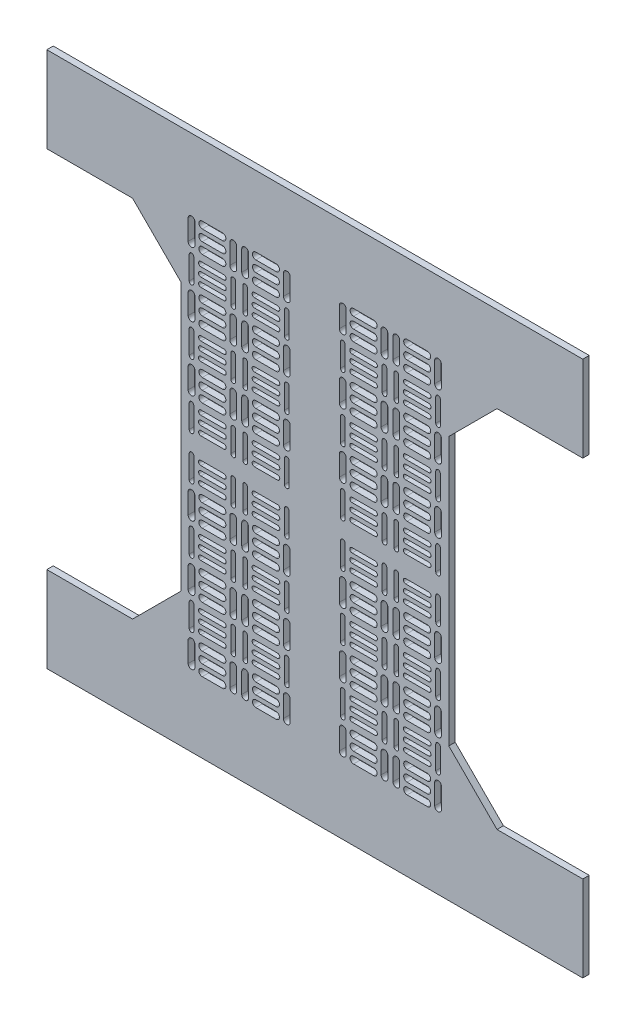
SolidWorks part; units mm, degrees
ref_plane "XY" through (0, 0, 0) normal (0, 0, 1) x (1, 0, 0)
ref_plane "-XZ" through (0, 0, 0) normal (0, 1, 0) x (1, 0, 0)
ref_plane "ZY" through (0, 0, 0) normal (1, 0, 0) x (0, 0, -1)
sketch "Esquisse1" plane through (0, 0, 0) normal (0, 0, 1) x (1, 0, 0)
  line L0 (0, 0) -> (0, 125)
  line L13 (0, 125) -> (125, 125)
  line L19 (125, 125) -> (125, 85)
  line L20 (125, 85) -> (85, 85)
  line L21 (62.5, 62.5) -> (62.5, 0)
  line L22 (62.5, 0) -> (0, 0)
  line L23 (85, 85) -> (62.5, 62.5)
  dimension "D1" = 40
  dimension "D4" = 125
  dimension "D2" = 40
  dimension "D3" = 125
  dimension "D5" = 62.5
  dimension "D6" = 62.5
extrude "Boss.-Extru.1" add sketch "Esquisse1" along normal blind 3
sketch "Esquisse2" plane through (0, 0, 3) normal (0, 0, 1) x (1, 0, 0)
  line L0 (43.05, 83.7) -> (52.5, 83.7)
  line L3 (43.05, 90.425) -> (52.5, 90.425) construction
  line L4 (43.05, 92) -> (52.5, 92)
  line L5 (43.05, 88.85) -> (52.5, 88.85)
  line L6 (57.5, 90) -> (57.5, 80.55) construction
  line L7 (59.075, 90) -> (59.075, 80.55)
  line L8 (55.925, 90) -> (55.925, 80.55)
  line L9 (0, 125) -> (125, 125) construction
  line L10 (62.5, 62.5) -> (62.5, 0) construction
  line L11 (43.05, 86.85) -> (52.5, 86.85)
  line L12 (43.05, 78.55) -> (52.5, 78.55)
  line L13 (43.05, 81.7) -> (52.5, 81.7)
  line L18 (42.4, 74.325) -> (53.15, 74.325) construction
  line L28 (47.775, 92) -> (47.775, 88.85) construction
  line L29 (42.4, 75.4) -> (53.15, 75.4)
  line L30 (36.475, 90) -> (36.475, 80.55)
  line L31 (39.625, 90) -> (39.625, 80.55)
  line L32 (42.4, 73.25) -> (53.15, 73.25)
  line L34 (57.5, 64.8) -> (57.5, 75.55) construction
  line L35 (56.425, 75.55) -> (56.425, 64.8)
  line L36 (58.575, 75.55) -> (58.575, 64.8)
  line L37 (47.775, 73.25) -> (47.775, 75.4) construction
  line L38 (42.4, 69.1) -> (53.15, 69.1)
  line L39 (42.4, 71.25) -> (53.15, 71.25)
  line L40 (42.4, 64.95) -> (53.15, 64.95)
  line L41 (42.4, 67.1) -> (53.15, 67.1)
  line L42 (39.125, 75.55) -> (39.125, 64.8)
  line L43 (36.975, 75.55) -> (36.975, 64.8)
  circle A5 centre (43.05, 90.425) radius 1.575 construction
  circle A6 centre (46.2, 90.425) radius 1.575 construction
  circle A7 centre (49.35, 90.425) radius 1.575 construction
  circle A8 centre (52.5, 90.425) radius 1.575 construction
  arc A9 (43.05, 92) -> (43.05, 88.85) centre (43.05, 90.425) ccw
  arc A10 (52.5, 92) -> (52.5, 88.85) centre (52.5, 90.425) cw
  circle A11 centre (57.5, 90) radius 1.575 construction
  circle A12 centre (57.5, 86.85) radius 1.575 construction
  circle A13 centre (57.5, 83.7) radius 1.575 construction
  circle A14 centre (57.5, 80.55) radius 1.575 construction
  arc A15 (59.075, 90) -> (55.925, 90) centre (57.5, 90) ccw
  arc A16 (59.075, 80.55) -> (55.925, 80.55) centre (57.5, 80.55) cw
  arc A17 (52.5, 86.85) -> (52.5, 83.7) centre (52.5, 85.275) cw
  arc A18 (43.05, 86.85) -> (43.05, 83.7) centre (43.05, 85.275) ccw
  arc A19 (52.5, 81.7) -> (52.5, 78.55) centre (52.5, 80.125) cw
  arc A20 (43.05, 81.7) -> (43.05, 78.55) centre (43.05, 80.125) ccw
  arc A41 (36.475, 90) -> (39.625, 90) centre (38.05, 90) cw
  arc A42 (36.475, 80.55) -> (39.625, 80.55) centre (38.05, 80.55) ccw
  circle A45 centre (42.4, 74.325) radius 1.075 construction
  circle A46 centre (44.55, 74.325) radius 1.075 construction
  circle A47 centre (46.7, 74.325) radius 1.075 construction
  circle A48 centre (51, 74.325) radius 1.075 construction
  circle A49 centre (53.15, 74.325) radius 1.075 construction
  circle A50 centre (48.85, 74.325) radius 1.075 construction
  arc A51 (42.4, 75.4) -> (42.4, 73.25) centre (42.4, 74.325) ccw
  arc A52 (53.15, 75.4) -> (53.15, 73.25) centre (53.15, 74.325) cw
  circle A53 centre (57.5, 75.55) radius 1.075 construction
  circle A54 centre (57.5, 64.8) radius 1.075 construction
  circle A55 centre (57.5, 66.95) radius 1.075 construction
  circle A56 centre (57.5, 69.1) radius 1.075 construction
  circle A57 centre (57.5, 71.25) radius 1.075 construction
  circle A58 centre (57.5, 73.4) radius 1.075 construction
  arc A59 (56.425, 75.55) -> (58.575, 75.55) centre (57.5, 75.55) cw
  arc A60 (56.425, 64.8) -> (58.575, 64.8) centre (57.5, 64.8) ccw
  arc A61 (53.15, 71.25) -> (53.15, 69.1) centre (53.15, 70.175) cw
  arc A62 (42.4, 71.25) -> (42.4, 69.1) centre (42.4, 70.175) ccw
  arc A63 (53.15, 67.1) -> (53.15, 64.95) centre (53.15, 66.025) cw
  arc A64 (42.4, 67.1) -> (42.4, 64.95) centre (42.4, 66.025) ccw
  arc A65 (39.125, 64.8) -> (36.975, 64.8) centre (38.05, 64.8) cw
  arc A66 (39.125, 75.55) -> (36.975, 75.55) centre (38.05, 75.55) ccw
  point P11 (47.775, 90.425)
  point P41 (57.5, 85.275)
  point P42 (47.775, 74.325)
  point P62 (57.5, 70.175)
  point P83 (47.775, 90.425)
  point P86 (47.775, 74.325)
  dimension "D1" = 3
  dimension "D2" = 3.15
  dimension "D4" = 35
  dimension "D6" = 2
  dimension "D8" = 2.15
  dimension "D3" = 5
  dimension "D5" = 5
  dimension "D9" = 5
  dimension "D10" = 3
  dimension "D11" = 2
extrude "Enlèv. mat.-Extru.1" cut sketch "Esquisse2" against normal through all both and the other way through all
pattern_linear "Répétition linéaire1" count 2 spacing 25 along (-1, 0, 0) count 3 spacing 30 along (0, -1, 0) of "Enlèv. mat.-Extru.1"
mirror "Symétrie1" about plane through (0, 0, 0) normal (0, 1, 0) of "Répétition linéaire1", "Enlèv. mat.-Extru.1", "Boss.-Extru.1"
mirror "Symétrie2" about plane through (0, 0, 0) normal (1, 0, 0) of "Symétrie1", "Boss.-Extru.1", "Enlèv. mat.-Extru.1", "Répétition linéaire1"
equation "\"D2@Esquisse1\"=\"D1@Esquisse1\""
equation "\"D5@Esquisse1\"=\"D3@Esquisse1\"/2"
equation "\"D6@Esquisse1\"=\"D4@Esquisse1\"/2"
